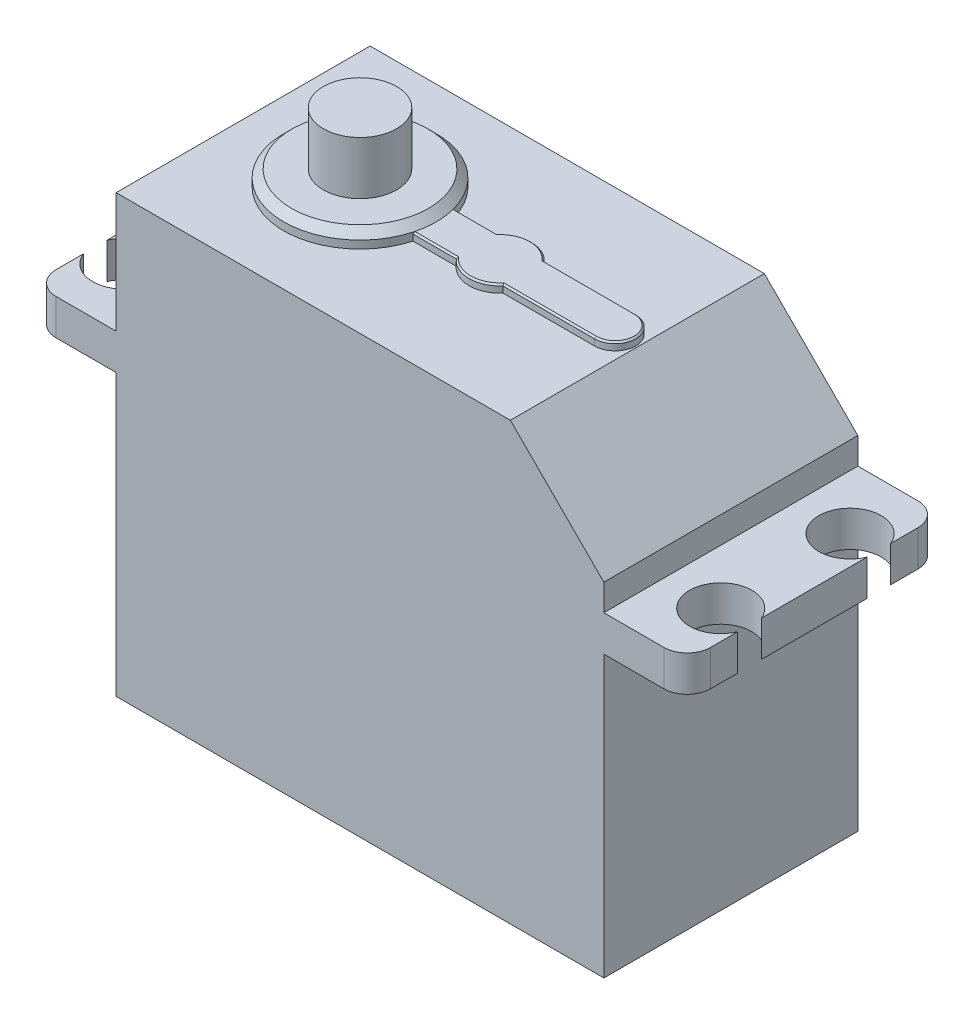
SolidWorks part; units mm, degrees
ref_plane "Front Plane" through (0, 0, 0) normal (0, 0, 1) x (1, 0, 0)
ref_plane "Top Plane" through (0, 0, 0) normal (0, 1, 0) x (1, 0, 0)
ref_plane "Right Plane" through (0, 0, 0) normal (1, 0, 0) x (0, 0, -1)
sketch "Sketch1" plane through (0, 0, 0) normal (0, 1, 0) x (1, 0, 0)
  line L1 (-15.65, 8.15) -> (15.65, 8.15)
  line L2 (-15.65, 8.15) -> (-15.65, -8.15)
  line L3 (-15.65, -8.15) -> (15.65, -8.15)
  line L4 (15.65, 8.15) -> (15.65, -8.15)
  line L5 (-15.65, 8.15) -> (15.65, -8.15) construction
  line L6 (-15.65, -8.15) -> (15.65, 8.15) construction
  point P0 (0, 0)
extrude "Boss-Extrude1" add sketch "Sketch1" along normal blind 28
chamfer "Chamfer1" distance 6 angle 45 1 edges at (15.65, 28, 0)
ref_plane "Plane1" through (0, 18, 0) normal (0, -1, 0) x (-1, 0, 0)
sketch "Sketch2" plane through (0, 18, 0) normal (0, -1, 0) x (-1, 0, 0)
  line L0 (15.65, 8.15) -> (15.65, -8.15) construction
  line L1 (19.5, 8.15) -> (-19.5, 8.15)
  line L2 (21, 6.65) -> (21, 4.9099)
  line L3 (19.5, -8.15) -> (-19.5, -8.15)
  line L4 (-21, 6.65) -> (-21, 4.9099)
  line L5 (21, 8.15) -> (-21, -8.15) construction
  line L6 (21, -8.15) -> (-21, 8.15) construction
  line L7 (21.5, 0) -> (25.5052, 0) construction
  line L8 (0, 8.15) -> (0, 17.7192) construction
  line L9 (21, 3.3901) -> (21, -3.3901)
  line L10 (21, -4.9099) -> (21, -6.65)
  line L11 (-21, 3.3901) -> (-21, -3.3901)
  line L12 (-21, -4.9099) -> (-21, -6.65)
  arc A0 (21, 4.9099) -> (21, 3.3901) centre (19.15, 4.15) ccw
  arc A1 (21, -4.9099) -> (21, -3.3901) centre (19.15, -4.15) cw
  arc A2 (-21, -4.9099) -> (-21, -3.3901) centre (-19.15, -4.15) ccw
  arc A3 (-21, 4.9099) -> (-21, 3.3901) centre (-19.15, 4.15) cw
  arc A4 (21, -6.65) -> (19.5, -8.15) centre (19.5, -6.65) cw
  arc A5 (-19.5, -8.15) -> (-21, -6.65) centre (-19.5, -6.65) cw
  arc A6 (-21, 6.65) -> (-19.5, 8.15) centre (-19.5, 6.65) cw
  arc A7 (19.5, 8.15) -> (21, 6.65) centre (19.5, 6.65) cw
  point P0 (0, 0)
  dimension "D1" = 3.5
  dimension "D2" = 4
  dimension "D3" = 1.5
extrude "Boss-Extrude2" add sketch "Sketch2" against normal blind 2.3
sketch "Sketch4" plane through (0, 28, 0) normal (0, 1, 0) x (1, 0, 0)
  line L0 (-15.65, 8.15) -> (-15.65, -8.15) construction
  circle A0 centre (-8.15, 0) radius 4.9
  dimension "D1" = 7.5
extrude "Boss-Extrude3" add sketch "Sketch4" along normal blind 1
chamfer "Chamfer2" distance 0.5 angle 45 1 edges at (-8.15, 29, 4.9)
sketch "Sketch5" plane through (0, 29, 0) normal (0, 1, 0) x (1, 0, 0)
  circle A0 centre (-8.15, 0) radius 2.35
extrude "Boss-Extrude4" add sketch "Sketch5" along normal blind 3.4 separate body
sketch "Sketch6" plane through (0, 28, 0) normal (0, 1, 0) x (1, 0, 0)
  line L0 (-8.15, 2.35) -> (-8.15, 12.739) construction
  line L1 (-6.7394, 0) -> (8.224, 0) construction
  line L2 (-6.7394, 1.323) -> (-0.6499, 1.323)
  line L3 (-6.7394, -1.323) -> (-0.6499, -1.323)
  line L4 (2.3499, 1.323) -> (8.224, 1.323)
  line L5 (2.3499, -1.323) -> (8.224, -1.323)
  arc A0 (-0.6499, -1.323) -> (2.3499, -1.323) centre (0.85, 0) ccw
  arc A1 (-6.7394, 1.323) -> (-6.7394, -1.323) centre (-6.7394, 0) ccw
  arc A2 (8.224, -1.323) -> (8.224, 1.323) centre (8.224, 0) ccw
  arc A3 (2.3499, 1.323) -> (-0.6499, 1.323) centre (0.85, 0) ccw
  point P5 (0.7423, 0)
  dimension "D1" = 9
extrude "Boss-Extrude5" add sketch "Sketch6" along normal blind 0.5
chamfer "Chamfer3" distance 0.1 angle 45 7 edges at (-2.0409, 28.5, -1.323) (0.85, 28.5, -2) (5.287, 28.5, -1.323) (9.547, 28.5, 0) (-2.0409, 28.5, 1.323) (0.85, 28.5, 2) (5.287, 28.5, 1.323)
sketch "Sketch7" plane through (-15.65, 0, 0) normal (-1, 0, 0) x (0, 0, 1)
  line L0 (-8.15, 0) -> (8.15, 0) construction
  line L1 (-2.85, 6.6) -> (2.85, 6.6)
  line L2 (-2.85, 6.6) -> (-2.85, 4.1)
  line L3 (-2.85, 4.1) -> (2.85, 4.1)
  line L4 (2.85, 6.6) -> (2.85, 4.1)
  line L5 (-2.85, 6.6) -> (2.85, 4.1) construction
  line L6 (-2.85, 4.1) -> (2.85, 6.6) construction
  line L7 (0, 0) -> (0, 12.3497) construction
  point P0 (0, 5.35)
  dimension "D1" = 4.1
extrude "Boss-Extrude6" add sketch "Sketch7" along normal blind 1.5
